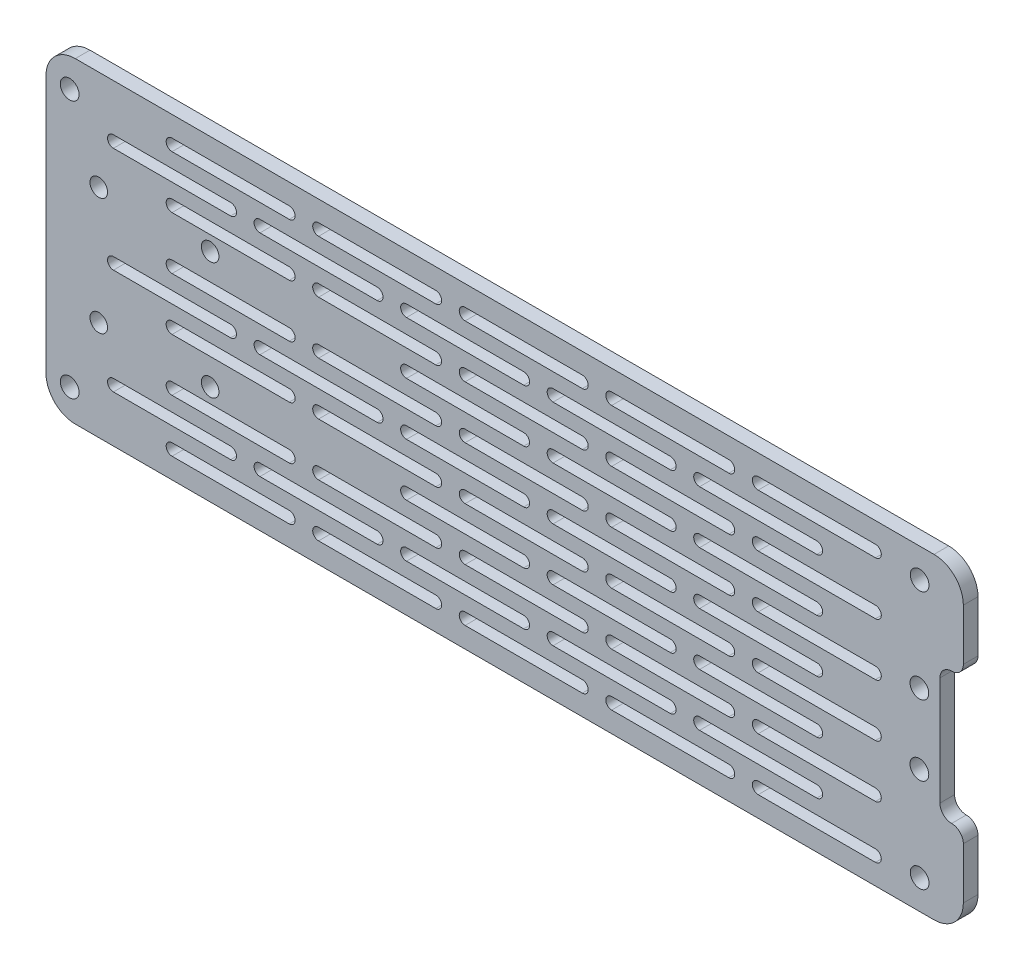
SolidWorks part; units mm, degrees
ref_plane "前视基准面" through (0, 0, 0) normal (0, 0, 1) x (1, 0, 0)
ref_plane "上视基准面" through (0, 0, 0) normal (0, 1, 0) x (1, 0, 0)
ref_plane "右视基准面" through (0, 0, 0) normal (1, 0, 0) x (0, 0, -1)
other "Configuration Table"
sketch "草图1" plane through (0, 0, 0) normal (0, 0, 1) x (1, 0, 0)
  line L1 (3.3, 37) -> (-153.2, 37)
  line L2 (3.3, 37) -> (3.3, -17)
  line L3 (3.3, -17) -> (-153.2, -17)
  line L4 (-153.2, 37) -> (-153.2, -17)
  dimension "D1" = 156.5
extrude "凸台-拉伸1" add sketch "草图1" along normal blind 2.5
fillet "圆角1" radius 5 4 edges at (-153.2, -17, 1.25) (-153.2, 37, 1.25) (3.3, 37, 1.25) (3.3, -17, 1.25)
sketch "草图2" plane through (0, 0, 2.5) normal (0, 0, 1) x (1, 0, 0)
  line L0 (-104.525, 10) -> (80.9664, 10) construction
  line L1 (-148.2, -17) -> (-1.7, -17) construction
  line L3 (-1.7, 37) -> (-148.2, 37) construction
  line L4 (3.3, -12) -> (3.3, 32) construction
  line L5 (3.3, -1.25) -> (-0.7, -1.25)
  line L6 (3.3, -1.25) -> (3.3, 21.25)
  line L7 (3.3, 21.25) -> (-0.7, 21.25)
  line L8 (-0.7, -1.25) -> (-0.7, 21.25)
  line L9 (-74.95, 71.5173) -> (-74.95, -58.776) construction
  line L10 (-153.2, 32) -> (-153.2, -12) construction
  line L11 (-45.375, 10) -> (-230.8664, 10) construction
  line L19 (-150.7, 27) -> (-142.7, 27) construction
  line L20 (-150.7, 27) -> (-150.7, 13.5) construction
  line L21 (-150.7, 13.5) -> (-118.7, 13.5) construction
  line L22 (-118.7, 27) -> (-118.7, 13.5) construction
  line L25 (-142.7, 27) -> (-142.7, 23.5) construction
  line L27 (-142.7, 23.5) -> (-126.7, 23.5) construction
  line L28 (-126.7, 23.5) -> (-126.7, 27) construction
  line L29 (-126.7, 27) -> (-118.7, 27) construction
  circle A0 centre (-4.2, 4) radius 1.6
  circle A1 centre (-4.2, 16) radius 1.6
  circle A11 centre (-125.2, 20) radius 1.5
  circle A12 centre (-144.2, 20) radius 1.5
  circle A13 centre (-125.2, 0) radius 1.5
  circle A14 centre (-144.2, 0) radius 1.5
  point P26 (-138.1207, 10)
  point P29 (-125.2, 18.5)
  point P30 (-123.7, 20)
  point P43 (-138.1207, 10)
  point P52 (-133.2793, 10)
  dimension "D4" = 3.2
  dimension "D8" = 5
  dimension "D11" = 19
  dimension "D12" = 2.5
  dimension "D13" = 13.5
  dimension "D16" = 10
  dimension "D9" = 3
  dimension "D10" = 3
  dimension "D1" = 4
  dimension "D2" = 7.5
  dimension "D3" = 12
  dimension "D5" = 22.5
  dimension "D6" = 32
  dimension "D7" = 5
  dimension "D15" = 8
  dimension "D14" = 16
  dimension "D17" = 3.5
  dimension "D18" = 19
extrude "切除-拉伸1" cut sketch "草图2" against normal up to next contours A1 | A0 | L6 L5 L8 L7 | A12 | A11 | A14 | A13
fillet "圆角5" radius 2 4 edges at (3.3, 21.25, 1.25) (-0.7, 21.25, 1.25) (-0.7, -1.25, 1.25) (3.3, -1.25, 1.25)
sketch "草图3" plane through (0, 0, 2.5) normal (0, 0, 1) x (1, 0, 0)
  line L1 (-156.66, 39.5) -> (-156.66, 114.5) construction
  line L2 (3.34, 37.5) -> (-156.66, 37.5) construction
  line L3 (-76.66, -135.6292) -> (-76.66, 162.1553) construction
  line L4 (-198.0876, 10) -> (29.1796, 10) construction
  line L5 (-156.66, -19.5) -> (-156.66, -100.5) construction
  line L6 (3.34, -19.5) -> (3.34, -100.5) construction
  line L7 (-148.2, -17) -> (-1.7, -17) construction
  line L8 (-1.7, 37) -> (-148.2, 37) construction
  line L9 (3.34, 114.5) -> (3.34, 39.5) construction
  line L10 (-156.66, 30.7638) -> (-156.66, 35.5) construction
  circle A0 centre (-149.16, 32) radius 1.6
  circle A1 centre (-149.16, -12) radius 1.6
  circle A2 centre (-4.16, 32) radius 1.6
  circle A3 centre (-4.16, -12) radius 1.6
  dimension "D1" = 3.2
  dimension "D2" = 7.5
  dimension "D3" = 5.5
  dimension "D4" = 45.6
extrude "切除-拉伸2" cut sketch "草图3" against normal up to next
sketch "草图4" plane through (0, 0, 2.5) normal (0, 0, 1) x (1, 0, 0)
  line L0 (-11.7, -12.5) -> (-31.7, -12.5) construction
  line L1 (-11.7, -13.5) -> (-31.7, -13.5)
  line L2 (-11.7, -11.5) -> (-31.7, -11.5)
  line L3 (3.3, -12) -> (3.3, -3.25) construction
  line L4 (-148.2, -17) -> (-1.7, -17) construction
  line L5 (-111.7, -12.5) -> (-131.7, -12.5) construction
  line L7 (-11.7, -2.5) -> (-31.7, -2.5)
  line L8 (-11.7, -4.5) -> (-31.7, -4.5)
  line L9 (-11.7, -3.5) -> (-31.7, -3.5) construction
  line L10 (-11.7, 6.5) -> (-31.7, 6.5)
  line L11 (-11.7, 4.5) -> (-31.7, 4.5)
  line L12 (-11.7, 5.5) -> (-31.7, 5.5) construction
  line L13 (-11.7, 15.5) -> (-31.7, 15.5)
  line L14 (-11.7, 13.5) -> (-31.7, 13.5)
  line L15 (-11.7, 14.5) -> (-31.7, 14.5) construction
  line L16 (-11.7, 24.5) -> (-31.7, 24.5)
  line L17 (-11.7, 22.5) -> (-31.7, 22.5)
  line L18 (-11.7, 23.5) -> (-31.7, 23.5) construction
  line L19 (-11.7, 33.5) -> (-31.7, 33.5)
  line L20 (-11.7, 31.5) -> (-31.7, 31.5)
  line L21 (-11.7, 32.5) -> (-31.7, 32.5) construction
  line L22 (-11.7, -11.5) -> (-11.7, -2.5) construction
  line L23 (-41.7, -8) -> (-21.7, -8) construction
  line L24 (-41.7, -7) -> (-21.7, -7)
  line L25 (-41.7, -9) -> (-21.7, -9)
  line L26 (-41.7, 0) -> (-21.7, 0)
  line L27 (-41.7, 2) -> (-21.7, 2)
  line L28 (-41.7, 1) -> (-21.7, 1) construction
  line L29 (-41.7, 9) -> (-21.7, 9)
  line L30 (-41.7, 11) -> (-21.7, 11)
  line L31 (-41.7, 10) -> (-21.7, 10) construction
  line L32 (-41.7, 18) -> (-21.7, 18)
  line L33 (-41.7, 20) -> (-21.7, 20)
  line L34 (-41.7, 19) -> (-21.7, 19) construction
  line L35 (-41.7, 27) -> (-21.7, 27)
  line L36 (-41.7, 29) -> (-21.7, 29)
  line L37 (-41.7, 28) -> (-21.7, 28) construction
  line L38 (-116.7, -8) -> (-96.7, -8) construction
  line L39 (-36.7, -11.5) -> (-36.7, -2.5) construction
  line L40 (-36.7, -12.5) -> (-56.7, -12.5) construction
  line L41 (-36.7, -13.5) -> (-56.7, -13.5)
  line L42 (-36.7, -11.5) -> (-56.7, -11.5)
  line L43 (-36.7, -3.5) -> (-56.7, -3.5) construction
  line L44 (-36.7, -4.5) -> (-56.7, -4.5)
  line L45 (-36.7, -2.5) -> (-56.7, -2.5)
  line L46 (-36.7, 5.5) -> (-56.7, 5.5) construction
  line L47 (-36.7, 4.5) -> (-56.7, 4.5)
  line L48 (-36.7, 6.5) -> (-56.7, 6.5)
  line L49 (-36.7, 14.5) -> (-56.7, 14.5) construction
  line L50 (-36.7, 13.5) -> (-56.7, 13.5)
  line L51 (-36.7, 15.5) -> (-56.7, 15.5)
  line L52 (-36.7, 23.5) -> (-56.7, 23.5) construction
  line L53 (-36.7, 22.5) -> (-56.7, 22.5)
  line L54 (-36.7, 24.5) -> (-56.7, 24.5)
  line L55 (-36.7, 32.5) -> (-56.7, 32.5) construction
  line L56 (-36.7, 31.5) -> (-56.7, 31.5)
  line L57 (-36.7, 33.5) -> (-56.7, 33.5)
  line L58 (-66.7, -8) -> (-46.7, -8) construction
  line L59 (-66.7, -7) -> (-46.7, -7)
  line L60 (-66.7, -9) -> (-46.7, -9)
  line L61 (-66.7, 1) -> (-46.7, 1) construction
  line L62 (-66.7, 2) -> (-46.7, 2)
  line L63 (-66.7, 0) -> (-46.7, 0)
  line L64 (-66.7, 10) -> (-46.7, 10) construction
  line L65 (-66.7, 11) -> (-46.7, 11)
  line L66 (-66.7, 9) -> (-46.7, 9)
  line L67 (-66.7, 19) -> (-46.7, 19) construction
  line L68 (-66.7, 20) -> (-46.7, 20)
  line L69 (-66.7, 18) -> (-46.7, 18)
  line L70 (-66.7, 28) -> (-46.7, 28) construction
  line L71 (-66.7, 29) -> (-46.7, 29)
  line L72 (-66.7, 27) -> (-46.7, 27)
  line L73 (-61.7, -11.5) -> (-61.7, -2.5) construction
  line L74 (-61.7, -12.5) -> (-81.7, -12.5) construction
  line L75 (-61.7, -13.5) -> (-81.7, -13.5)
  line L76 (-61.7, -11.5) -> (-81.7, -11.5)
  line L77 (-61.7, -3.5) -> (-81.7, -3.5) construction
  line L78 (-61.7, -4.5) -> (-81.7, -4.5)
  line L79 (-61.7, -2.5) -> (-81.7, -2.5)
  line L80 (-61.7, 5.5) -> (-81.7, 5.5) construction
  line L81 (-61.7, 4.5) -> (-81.7, 4.5)
  line L82 (-61.7, 6.5) -> (-81.7, 6.5)
  line L83 (-61.7, 14.5) -> (-81.7, 14.5) construction
  line L84 (-61.7, 13.5) -> (-81.7, 13.5)
  line L85 (-61.7, 15.5) -> (-81.7, 15.5)
  line L86 (-61.7, 23.5) -> (-81.7, 23.5) construction
  line L87 (-61.7, 22.5) -> (-81.7, 22.5)
  line L88 (-61.7, 24.5) -> (-81.7, 24.5)
  line L89 (-61.7, 32.5) -> (-81.7, 32.5) construction
  line L90 (-61.7, 31.5) -> (-81.7, 31.5)
  line L91 (-61.7, 33.5) -> (-81.7, 33.5)
  line L92 (-91.7, -8) -> (-71.7, -8) construction
  line L93 (-91.7, -7) -> (-71.7, -7)
  line L94 (-91.7, -9) -> (-71.7, -9)
  line L95 (-91.7, 1) -> (-71.7, 1) construction
  line L96 (-91.7, 2) -> (-71.7, 2)
  line L97 (-91.7, 0) -> (-71.7, 0)
  line L98 (-91.7, 10) -> (-71.7, 10) construction
  line L99 (-91.7, 11) -> (-71.7, 11)
  line L100 (-91.7, 9) -> (-71.7, 9)
  line L101 (-91.7, 19) -> (-71.7, 19) construction
  line L102 (-91.7, 20) -> (-71.7, 20)
  line L103 (-91.7, 18) -> (-71.7, 18)
  line L104 (-91.7, 28) -> (-71.7, 28) construction
  line L105 (-91.7, 29) -> (-71.7, 29)
  line L106 (-91.7, 27) -> (-71.7, 27)
  line L107 (-86.7, -11.5) -> (-86.7, -2.5) construction
  line L108 (-86.7, -12.5) -> (-106.7, -12.5) construction
  line L109 (-86.7, -13.5) -> (-106.7, -13.5)
  line L110 (-86.7, -11.5) -> (-106.7, -11.5)
  line L111 (-86.7, -3.5) -> (-106.7, -3.5) construction
  line L112 (-86.7, -4.5) -> (-106.7, -4.5)
  line L113 (-86.7, -2.5) -> (-106.7, -2.5)
  line L114 (-86.7, 5.5) -> (-106.7, 5.5) construction
  line L115 (-86.7, 4.5) -> (-106.7, 4.5)
  line L116 (-86.7, 6.5) -> (-106.7, 6.5)
  line L117 (-86.7, 14.5) -> (-106.7, 14.5) construction
  line L118 (-86.7, 13.5) -> (-106.7, 13.5)
  line L119 (-86.7, 15.5) -> (-106.7, 15.5)
  line L120 (-86.7, 23.5) -> (-106.7, 23.5) construction
  line L121 (-86.7, 22.5) -> (-106.7, 22.5)
  line L122 (-86.7, 24.5) -> (-106.7, 24.5)
  line L123 (-86.7, 32.5) -> (-106.7, 32.5) construction
  line L124 (-86.7, 31.5) -> (-106.7, 31.5)
  line L125 (-86.7, 33.5) -> (-106.7, 33.5)
  line L129 (-111.7, -13.5) -> (-131.7, -13.5)
  line L138 (-111.7, -11.5) -> (-131.7, -11.5)
  line L141 (-11.7, -11.5) -> (-36.7, -11.5) construction
  line L148 (-111.7, -3.5) -> (-131.7, -3.5) construction
  line L151 (-111.7, -4.5) -> (-131.7, -4.5)
  line L154 (-111.7, -2.5) -> (-131.7, -2.5)
  line L157 (-111.7, 5.5) -> (-131.7, 5.5) construction
  line L160 (-111.7, 4.5) -> (-131.7, 4.5)
  line L163 (-111.7, 6.5) -> (-131.7, 6.5)
  line L166 (-111.7, 14.5) -> (-131.7, 14.5) construction
  line L171 (-111.7, 13.5) -> (-131.7, 13.5)
  line L172 (-111.7, 15.5) -> (-131.7, 15.5)
  line L173 (-111.7, 23.5) -> (-131.7, 23.5) construction
  line L174 (-111.7, 22.5) -> (-131.7, 22.5)
  line L175 (-111.7, 24.5) -> (-131.7, 24.5)
  line L176 (-111.7, 32.5) -> (-131.7, 32.5) construction
  line L177 (-111.7, 31.5) -> (-131.7, 31.5)
  line L178 (-111.7, 33.5) -> (-131.7, 33.5)
  line L179 (-116.7, -7) -> (-96.7, -7)
  line L180 (-116.7, -9) -> (-96.7, -9)
  line L181 (-116.7, 10) -> (-96.7, 10) construction
  line L182 (-116.7, 11) -> (-96.7, 11)
  line L183 (-116.7, 9) -> (-96.7, 9)
  line L184 (-116.7, 28) -> (-96.7, 28) construction
  line L185 (-116.7, 29) -> (-96.7, 29)
  line L186 (-116.7, 27) -> (-96.7, 27)
  line L187 (-141.7, -8) -> (-121.7, -8) construction
  line L188 (-141.7, -7) -> (-121.7, -7)
  line L189 (-141.7, -9) -> (-121.7, -9)
  line L190 (-141.7, 10) -> (-121.7, 10) construction
  line L191 (-141.7, 11) -> (-121.7, 11)
  line L192 (-141.7, 9) -> (-121.7, 9)
  line L193 (-141.7, 28) -> (-121.7, 28) construction
  line L194 (-141.7, 29) -> (-121.7, 29)
  line L195 (-141.7, 27) -> (-121.7, 27)
  line L1242 (-116.7, -8) -> (-96.7, -8) construction
  line L1243 (-116.7, -7) -> (-96.7, -7) [skipped]
  line L1244 (-116.7, -9) -> (-96.7, -9) [skipped]
  line L1245 (-116.7, 1) -> (-96.7, 1) construction
  line L1246 (-116.7, 2) -> (-96.7, 2) [skipped]
  line L1247 (-116.7, 0) -> (-96.7, 0) [skipped]
  line L1248 (-116.7, 10) -> (-96.7, 10) construction
  line L1249 (-116.7, 11) -> (-96.7, 11) [skipped]
  line L1250 (-116.7, 9) -> (-96.7, 9) [skipped]
  line L1251 (-116.7, 19) -> (-96.7, 19) construction
  line L1252 (-116.7, 20) -> (-96.7, 20) [skipped]
  line L1253 (-116.7, 18) -> (-96.7, 18) [skipped]
  line L1254 (-116.7, 28) -> (-96.7, 28) construction
  line L1255 (-116.7, 29) -> (-96.7, 29) [skipped]
  line L1256 (-116.7, 27) -> (-96.7, 27) [skipped]
  line L1257 (-116.7, -8) -> (-96.7, -8) construction
  line L1258 (-116.7, -7) -> (-96.7, -7) [skipped]
  line L1259 (-116.7, -9) -> (-96.7, -9) [skipped]
  line L1260 (-116.7, 1) -> (-96.7, 1) construction
  line L1261 (-116.7, 2) -> (-96.7, 2) [skipped]
  line L1262 (-116.7, 0) -> (-96.7, 0) [skipped]
  line L1263 (-116.7, 10) -> (-96.7, 10) construction
  line L1264 (-116.7, 11) -> (-96.7, 11) [skipped]
  line L1265 (-116.7, 9) -> (-96.7, 9) [skipped]
  line L1266 (-116.7, 19) -> (-96.7, 19) construction
  line L1267 (-116.7, 20) -> (-96.7, 20) [skipped]
  line L1268 (-116.7, 18) -> (-96.7, 18) [skipped]
  line L1269 (-116.7, 28) -> (-96.7, 28) construction
  line L1270 (-116.7, 29) -> (-96.7, 29) [skipped]
  line L1271 (-116.7, 27) -> (-96.7, 27) [skipped]
  arc A0 (-11.7, -13.5) -> (-11.7, -11.5) centre (-11.7, -12.5) ccw
  arc A1 (-31.7, -11.5) -> (-31.7, -13.5) centre (-31.7, -12.5) ccw
  arc A2 (-11.7, -4.5) -> (-11.7, -2.5) centre (-11.7, -3.5) ccw
  arc A3 (-31.7, -2.5) -> (-31.7, -4.5) centre (-31.7, -3.5) ccw
  arc A4 (-11.7, 4.5) -> (-11.7, 6.5) centre (-11.7, 5.5) ccw
  arc A5 (-31.7, 6.5) -> (-31.7, 4.5) centre (-31.7, 5.5) ccw
  arc A6 (-11.7, 13.5) -> (-11.7, 15.5) centre (-11.7, 14.5) ccw
  arc A7 (-31.7, 15.5) -> (-31.7, 13.5) centre (-31.7, 14.5) ccw
  arc A8 (-11.7, 22.5) -> (-11.7, 24.5) centre (-11.7, 23.5) ccw
  arc A9 (-31.7, 24.5) -> (-31.7, 22.5) centre (-31.7, 23.5) ccw
  arc A10 (-11.7, 31.5) -> (-11.7, 33.5) centre (-11.7, 32.5) ccw
  arc A11 (-31.7, 33.5) -> (-31.7, 31.5) centre (-31.7, 32.5) ccw
  arc A12 (-41.7, -7) -> (-41.7, -9) centre (-41.7, -8) ccw
  arc A13 (-21.7, -9) -> (-21.7, -7) centre (-21.7, -8) ccw
  arc A14 (-41.7, 2) -> (-41.7, 0) centre (-41.7, 1) ccw
  arc A15 (-21.7, 0) -> (-21.7, 2) centre (-21.7, 1) ccw
  arc A16 (-41.7, 11) -> (-41.7, 9) centre (-41.7, 10) ccw
  arc A17 (-21.7, 9) -> (-21.7, 11) centre (-21.7, 10) ccw
  arc A18 (-41.7, 20) -> (-41.7, 18) centre (-41.7, 19) ccw
  arc A19 (-21.7, 18) -> (-21.7, 20) centre (-21.7, 19) ccw
  arc A20 (-41.7, 29) -> (-41.7, 27) centre (-41.7, 28) ccw
  arc A21 (-21.7, 27) -> (-21.7, 29) centre (-21.7, 28) ccw
  arc A22 (-36.7, -13.5) -> (-36.7, -11.5) centre (-36.7, -12.5) ccw
  arc A23 (-56.7, -11.5) -> (-56.7, -13.5) centre (-56.7, -12.5) ccw
  arc A24 (-36.7, -4.5) -> (-36.7, -2.5) centre (-36.7, -3.5) ccw
  arc A25 (-56.7, -2.5) -> (-56.7, -4.5) centre (-56.7, -3.5) ccw
  arc A26 (-36.7, 4.5) -> (-36.7, 6.5) centre (-36.7, 5.5) ccw
  arc A27 (-56.7, 6.5) -> (-56.7, 4.5) centre (-56.7, 5.5) ccw
  arc A28 (-36.7, 13.5) -> (-36.7, 15.5) centre (-36.7, 14.5) ccw
  arc A29 (-56.7, 15.5) -> (-56.7, 13.5) centre (-56.7, 14.5) ccw
  arc A30 (-36.7, 22.5) -> (-36.7, 24.5) centre (-36.7, 23.5) ccw
  arc A31 (-56.7, 24.5) -> (-56.7, 22.5) centre (-56.7, 23.5) ccw
  arc A32 (-36.7, 31.5) -> (-36.7, 33.5) centre (-36.7, 32.5) ccw
  arc A33 (-56.7, 33.5) -> (-56.7, 31.5) centre (-56.7, 32.5) ccw
  arc A34 (-66.7, -7) -> (-66.7, -9) centre (-66.7, -8) ccw
  arc A35 (-46.7, -9) -> (-46.7, -7) centre (-46.7, -8) ccw
  arc A36 (-66.7, 2) -> (-66.7, 0) centre (-66.7, 1) ccw
  arc A37 (-46.7, 0) -> (-46.7, 2) centre (-46.7, 1) ccw
  arc A38 (-66.7, 11) -> (-66.7, 9) centre (-66.7, 10) ccw
  arc A39 (-46.7, 9) -> (-46.7, 11) centre (-46.7, 10) ccw
  arc A40 (-66.7, 20) -> (-66.7, 18) centre (-66.7, 19) ccw
  arc A41 (-46.7, 18) -> (-46.7, 20) centre (-46.7, 19) ccw
  arc A42 (-66.7, 29) -> (-66.7, 27) centre (-66.7, 28) ccw
  arc A43 (-46.7, 27) -> (-46.7, 29) centre (-46.7, 28) ccw
  arc A44 (-61.7, -13.5) -> (-61.7, -11.5) centre (-61.7, -12.5) ccw
  arc A45 (-81.7, -11.5) -> (-81.7, -13.5) centre (-81.7, -12.5) ccw
  arc A46 (-61.7, -4.5) -> (-61.7, -2.5) centre (-61.7, -3.5) ccw
  arc A47 (-81.7, -2.5) -> (-81.7, -4.5) centre (-81.7, -3.5) ccw
  arc A48 (-61.7, 4.5) -> (-61.7, 6.5) centre (-61.7, 5.5) ccw
  arc A49 (-81.7, 6.5) -> (-81.7, 4.5) centre (-81.7, 5.5) ccw
  arc A50 (-61.7, 13.5) -> (-61.7, 15.5) centre (-61.7, 14.5) ccw
  arc A51 (-81.7, 15.5) -> (-81.7, 13.5) centre (-81.7, 14.5) ccw
  arc A52 (-61.7, 22.5) -> (-61.7, 24.5) centre (-61.7, 23.5) ccw
  arc A53 (-81.7, 24.5) -> (-81.7, 22.5) centre (-81.7, 23.5) ccw
  arc A54 (-61.7, 31.5) -> (-61.7, 33.5) centre (-61.7, 32.5) ccw
  arc A55 (-81.7, 33.5) -> (-81.7, 31.5) centre (-81.7, 32.5) ccw
  arc A56 (-91.7, -7) -> (-91.7, -9) centre (-91.7, -8) ccw
  arc A57 (-71.7, -9) -> (-71.7, -7) centre (-71.7, -8) ccw
  arc A58 (-91.7, 2) -> (-91.7, 0) centre (-91.7, 1) ccw
  arc A59 (-71.7, 0) -> (-71.7, 2) centre (-71.7, 1) ccw
  arc A60 (-91.7, 11) -> (-91.7, 9) centre (-91.7, 10) ccw
  arc A61 (-71.7, 9) -> (-71.7, 11) centre (-71.7, 10) ccw
  arc A62 (-91.7, 20) -> (-91.7, 18) centre (-91.7, 19) ccw
  arc A63 (-71.7, 18) -> (-71.7, 20) centre (-71.7, 19) ccw
  arc A64 (-91.7, 29) -> (-91.7, 27) centre (-91.7, 28) ccw
  arc A65 (-71.7, 27) -> (-71.7, 29) centre (-71.7, 28) ccw
  arc A66 (-86.7, -13.5) -> (-86.7, -11.5) centre (-86.7, -12.5) ccw
  arc A67 (-106.7, -11.5) -> (-106.7, -13.5) centre (-106.7, -12.5) ccw
  arc A68 (-86.7, -4.5) -> (-86.7, -2.5) centre (-86.7, -3.5) ccw
  arc A69 (-106.7, -2.5) -> (-106.7, -4.5) centre (-106.7, -3.5) ccw
  arc A70 (-86.7, 4.5) -> (-86.7, 6.5) centre (-86.7, 5.5) ccw
  arc A71 (-106.7, 6.5) -> (-106.7, 4.5) centre (-106.7, 5.5) ccw
  arc A72 (-86.7, 13.5) -> (-86.7, 15.5) centre (-86.7, 14.5) ccw
  arc A73 (-106.7, 15.5) -> (-106.7, 13.5) centre (-106.7, 14.5) ccw
  arc A74 (-86.7, 22.5) -> (-86.7, 24.5) centre (-86.7, 23.5) ccw
  arc A75 (-106.7, 24.5) -> (-106.7, 22.5) centre (-106.7, 23.5) ccw
  arc A76 (-86.7, 31.5) -> (-86.7, 33.5) centre (-86.7, 32.5) ccw
  arc A77 (-106.7, 33.5) -> (-106.7, 31.5) centre (-106.7, 32.5) ccw
  arc A114 (-111.7, -13.5) -> (-111.7, -11.5) centre (-111.7, -12.5) ccw
  arc A115 (-131.7, -11.5) -> (-131.7, -13.5) centre (-131.7, -12.5) ccw
  arc A116 (-111.7, -4.5) -> (-111.7, -2.5) centre (-111.7, -3.5) ccw
  arc A117 (-131.7, -2.5) -> (-131.7, -4.5) centre (-131.7, -3.5) ccw
  arc A118 (-111.7, 4.5) -> (-111.7, 6.5) centre (-111.7, 5.5) ccw
  arc A119 (-131.7, 6.5) -> (-131.7, 4.5) centre (-131.7, 5.5) ccw
  arc A120 (-111.7, 13.5) -> (-111.7, 15.5) centre (-111.7, 14.5) ccw
  arc A121 (-131.7, 15.5) -> (-131.7, 13.5) centre (-131.7, 14.5) ccw
  arc A122 (-111.7, 22.5) -> (-111.7, 24.5) centre (-111.7, 23.5) ccw
  arc A123 (-131.7, 24.5) -> (-131.7, 22.5) centre (-131.7, 23.5) ccw
  arc A124 (-111.7, 31.5) -> (-111.7, 33.5) centre (-111.7, 32.5) ccw
  arc A125 (-131.7, 33.5) -> (-131.7, 31.5) centre (-131.7, 32.5) ccw
  arc A126 (-116.7, -7) -> (-116.7, -9) centre (-116.7, -8) ccw
  arc A127 (-96.7, -9) -> (-96.7, -7) centre (-96.7, -8) ccw
  arc A128 (-116.7, 11) -> (-116.7, 9) centre (-116.7, 10) ccw
  arc A129 (-96.7, 9) -> (-96.7, 11) centre (-96.7, 10) ccw
  arc A130 (-116.7, 29) -> (-116.7, 27) centre (-116.7, 28) ccw
  arc A131 (-96.7, 27) -> (-96.7, 29) centre (-96.7, 28) ccw
  arc A132 (-141.7, -7) -> (-141.7, -9) centre (-141.7, -8) ccw
  arc A133 (-121.7, -9) -> (-121.7, -7) centre (-121.7, -8) ccw
  arc A134 (-141.7, 11) -> (-141.7, 9) centre (-141.7, 10) ccw
  arc A135 (-121.7, 9) -> (-121.7, 11) centre (-121.7, 10) ccw
  arc A136 (-141.7, 29) -> (-141.7, 27) centre (-141.7, 28) ccw
  arc A137 (-121.7, 27) -> (-121.7, 29) centre (-121.7, 28) ccw
  arc A836 (-116.7, -7) -> (-116.7, -9) centre (-116.7, -8) ccw [skipped]
  arc A837 (-96.7, -9) -> (-96.7, -7) centre (-96.7, -8) ccw [skipped]
  arc A838 (-116.7, 2) -> (-116.7, 0) centre (-116.7, 1) ccw [skipped]
  arc A839 (-96.7, 0) -> (-96.7, 2) centre (-96.7, 1) ccw [skipped]
  arc A840 (-116.7, 11) -> (-116.7, 9) centre (-116.7, 10) ccw [skipped]
  arc A841 (-96.7, 9) -> (-96.7, 11) centre (-96.7, 10) ccw [skipped]
  arc A842 (-116.7, 20) -> (-116.7, 18) centre (-116.7, 19) ccw [skipped]
  arc A843 (-96.7, 18) -> (-96.7, 20) centre (-96.7, 19) ccw [skipped]
  arc A844 (-116.7, 29) -> (-116.7, 27) centre (-116.7, 28) ccw [skipped]
  arc A845 (-96.7, 27) -> (-96.7, 29) centre (-96.7, 28) ccw [skipped]
  point P2 (-21.7, -12.5)
  point P9 (-31.7, -8)
  point P15 (-21.7, -3.5)
  point P22 (-21.7, 5.5)
  point P29 (-21.7, 14.5)
  point P36 (-21.7, 23.5)
  point P43 (-21.7, 32.5)
  point P55 (-31.7, 1)
  point P63 (-31.7, 10)
  point P70 (-31.7, 19)
  point P77 (-31.7, 28)
  point P85 (-106.7, -8)
  point P89 (-46.7, -12.5)
  point P94 (-56.7, -8)
  point P98 (-46.7, -3.5)
  point P105 (-46.7, 5.5)
  point P112 (-46.7, 14.5)
  point P119 (-46.7, 23.5)
  point P126 (-46.7, 32.5)
  point P138 (-56.7, 1)
  point P145 (-56.7, 10)
  point P152 (-56.7, 19)
  point P159 (-56.7, 28)
  point P168 (-71.7, -12.5)
  point P173 (-81.7, -8)
  point P177 (-71.7, -3.5)
  point P184 (-71.7, 5.5)
  point P191 (-71.7, 14.5)
  point P198 (-71.7, 23.5)
  point P205 (-71.7, 32.5)
  point P217 (-81.7, 1)
  point P224 (-81.7, 10)
  point P231 (-81.7, 19)
  point P238 (-81.7, 28)
  point P247 (-96.7, -12.5)
  point P254 (-121.7, -12.5)
  point P256 (-96.7, -3.5)
  point P263 (-96.7, 5.5)
  point P270 (-96.7, 14.5)
  point P277 (-96.7, 23.5)
  point P284 (-96.7, 32.5)
  point P291 (-102.2793, 1)
  point P298 (-102.2793, 10)
  point P299 (-121.7, -3.5)
  point P305 (-102.2793, 19)
  point P307 (-121.7, 5.5)
  point P312 (-102.2793, 28)
  point P315 (-121.7, 14.5)
  point P322 (-121.7, 23.5)
  point P331 (-121.7, 32.5)
  point P342 (-102.2793, -8)
  point P343 (-106.7, 10)
  point P349 (-102.2793, -8)
  point P351 (-106.7, 28)
  point P356 (-102.2793, 1)
  point P359 (-131.7, -8)
  point P363 (-102.2793, 10)
  point P367 (-131.7, 10)
  point P370 (-102.2793, 19)
  point P375 (-131.7, 28)
  point P377 (-102.2793, 28)
  point P384 (-102.2793, -8)
  point P391 (-102.2793, 1)
  point P398 (-102.2793, 10)
  point P405 (-102.2793, 19)
  point P412 (-102.2793, 28)
  point P419 (-102.2793, -8)
  point P426 (-102.2793, 1)
  point P433 (-102.2793, 10)
  point P440 (-102.2793, 19)
  point P447 (-102.2793, 28)
  point P454 (-102.2793, -8)
  point P461 (-102.2793, 1)
  point P468 (-102.2793, 10)
  point P475 (-102.2793, 19)
  point P482 (-102.2793, 28)
  point P489 (-102.2793, -8)
  point P496 (-102.2793, 1)
  point P503 (-102.2793, 10)
  point P510 (-102.2793, 19)
  point P517 (-102.2793, 28)
  point P524 (-102.2793, -8)
  point P531 (-102.2793, 1)
  point P538 (-102.2793, 10)
  point P545 (-102.2793, 19)
  point P552 (-102.2793, 28)
  point P559 (-102.2793, -8)
  point P566 (-102.2793, 1)
  point P573 (-102.2793, 10)
  point P580 (-102.2793, 19)
  point P587 (-102.2793, 28)
  point P594 (-102.2, -8)
  point P601 (-102.2, 1)
  point P608 (-102.2, 10)
  point P615 (-102.2, 19)
  point P622 (-102.2, 28)
  point P629 (-102.2, -8)
  point P636 (-102.2, 1)
  point P643 (-102.2, 10)
  point P650 (-102.2, 19)
  point P657 (-102.2, 28)
  point P664 (-102.2, -8)
  point P671 (-102.2, 1)
  point P678 (-102.2, 10)
  point P685 (-102.2, 19)
  point P692 (-102.2, 28)
  point P699 (-102.2, -8)
  point P706 (-102.2, 1)
  point P713 (-102.2, 10)
  point P720 (-102.2, 19)
  point P727 (-102.2, 28)
  point P734 (-102.2, -8)
  point P741 (-102.2, 1)
  point P748 (-102.2, 10)
  point P755 (-102.2, 19)
  point P762 (-102.2, 28)
  point P769 (-102.2, -8)
  point P776 (-102.2, 1)
  point P783 (-102.2, 10)
  point P790 (-102.2, 19)
  point P797 (-102.2, 28)
  point P804 (-102.2, -8)
  point P811 (-102.2, 1)
  point P818 (-102.2, 10)
  point P825 (-102.2, 19)
  point P832 (-102.2, 28)
  point P839 (-102.2, -8)
  point P846 (-102.2, 1)
  point P853 (-102.2, 10)
  point P860 (-102.2, 19)
  point P867 (-102.2, 28)
  point P874 (-107.26, -8)
  point P881 (-107.26, 1)
  point P888 (-107.26, 10)
  point P895 (-107.26, 19)
  point P902 (-107.26, 28)
  point P909 (-107.26, -8)
  point P916 (-107.26, 1)
  point P923 (-107.26, 10)
  point P930 (-107.26, 19)
  point P937 (-107.26, 28)
  point P944 (-106.2, -8)
  point P951 (-106.2, 1)
  point P958 (-106.2, 10)
  point P965 (-106.2, 19)
  point P972 (-106.2, 28)
  point P979 (-106.2, -8)
  point P986 (-106.2, 1)
  point P993 (-106.2, 10)
  point P1000 (-106.2, 19)
  point P1007 (-106.2, 28)
  point P1014 (-106.2, -8)
  point P1021 (-106.2, 1)
  point P1028 (-106.2, 10)
  point P1035 (-106.2, 19)
  point P1042 (-106.2, 28)
  point P1049 (-106.2, -8)
  point P1056 (-106.2, 1)
  point P1063 (-106.2, 10)
  point P1070 (-106.2, 19)
  point P1077 (-106.2, 28)
  point P1084 (-106.2, -8)
  point P1091 (-106.2, 1)
  point P1098 (-106.2, 10)
  point P1105 (-106.2, 19)
  point P1112 (-106.2, 28)
  point P1119 (-106.2, -8)
  point P1126 (-106.2, 1)
  point P1133 (-106.2, 10)
  point P1140 (-106.2, 19)
  point P1147 (-106.2, 28)
  point P1154 (-106.2, -8)
  point P1161 (-106.2, 1)
  point P1168 (-106.2, 10)
  point P1175 (-106.2, 19)
  point P1182 (-106.2, 28)
  point P1189 (-106.2, -8)
  point P1196 (-106.2, 1)
  point P1203 (-106.2, 10)
  point P1210 (-106.2, 19)
  point P1217 (-106.2, 28)
  point P1224 (-106.2, -8)
  point P1231 (-106.2, 1)
  point P1238 (-106.2, 10)
  point P1245 (-106.2, 19)
  point P1252 (-106.2, 28)
  point P1259 (-106.2, -8)
  point P1266 (-106.2, 1)
  point P1273 (-106.2, 10)
  point P1280 (-106.2, 19)
  point P1287 (-106.2, 28)
  point P1294 (-106.2, -8)
  point P1301 (-106.2, 1)
  point P1308 (-106.2, 10)
  point P1315 (-106.2, 19)
  point P1322 (-106.2, 28)
  point P1329 (-106.2, -8)
  point P1336 (-106.2, 1)
  point P1343 (-106.2, 10)
  point P1350 (-106.2, 19)
  point P1357 (-106.2, 28)
  point P1364 (-106.2, -8)
  point P1371 (-106.2, 1)
  point P1378 (-106.2, 10)
  point P1385 (-106.2, 19)
  point P1392 (-106.2, 28)
  point P1399 (-106.2, -8)
  point P1406 (-106.2, 1)
  point P1413 (-106.2, 10)
  point P1420 (-106.2, 19)
  point P1427 (-106.2, 28)
  point P1434 (-106.2, -8)
  point P1441 (-106.2, 1)
  point P1448 (-106.2, 10)
  point P1455 (-106.2, 19)
  point P1462 (-106.2, 28)
  point P1469 (-106.2, -8)
  point P1476 (-106.2, 1)
  point P1483 (-106.2, 10)
  point P1490 (-106.2, 19)
  point P1497 (-106.2, 28)
  point P1504 (-106.7, -8)
  point P1511 (-106.7, 1)
  point P1518 (-106.7, 10)
  point P1525 (-106.7, 19)
  point P1532 (-106.7, 28)
  point P1539 (-106.7, -8)
  point P1546 (-106.7, 1)
  point P1553 (-106.7, 10)
  point P1560 (-106.7, 19)
  point P1567 (-106.7, 28)
  point P1574 (-106.7, -8)
  point P1581 (-106.7, 1)
  point P1588 (-106.7, 10)
  point P1595 (-106.7, 19)
  point P1602 (-106.7, 28)
  point P1609 (-106.7, -8)
  point P1616 (-106.7, 1)
  point P1623 (-106.7, 10)
  point P1630 (-106.7, 19)
  point P1637 (-106.7, 28)
  point P1644 (-106.7, -8)
  point P1651 (-106.7, 1)
  point P1658 (-106.7, 10)
  point P1665 (-106.7, 19)
  point P1672 (-106.7, 28)
  point P1679 (-106.7, -8)
  point P1686 (-106.7, 1)
  point P1693 (-106.7, 10)
  point P1700 (-106.7, 19)
  point P1707 (-106.7, 28)
  point P1714 (-106.7, -8)
  point P1721 (-106.7, 1)
  point P1728 (-106.7, 10)
  point P1735 (-106.7, 19)
  point P1742 (-106.7, 28)
  point P1749 (-106.7, -8)
  point P1756 (-106.7, 1)
  point P1763 (-106.7, 10)
  point P1770 (-106.7, 19)
  point P1777 (-106.7, 28)
  point P1784 (-106.7, -8)
  point P1791 (-106.7, 1)
  point P1798 (-106.7, 10)
  point P1805 (-106.7, 19)
  point P1812 (-106.7, 28)
  point P1819 (-106.7, -8)
  point P1826 (-106.7, 1)
  point P1833 (-106.7, 10)
  point P1840 (-106.7, 19)
  point P1847 (-106.7, 28)
  point P1854 (-106.7, -8)
  point P1861 (-106.7, 1)
  point P1868 (-106.7, 10)
  point P1875 (-106.7, 19)
  point P1882 (-106.7, 28)
  point P1889 (-106.7, -8)
  point P1896 (-106.7, 1)
  point P1903 (-106.7, 10)
  point P1910 (-106.7, 19)
  point P1917 (-106.7, 28)
  point P1924 (-106.7, -8)
  point P1931 (-106.7, 1)
  point P1938 (-106.7, 10)
  point P1945 (-106.7, 19)
  point P1952 (-106.7, 28)
  point P1959 (-106.7, -8)
  point P1966 (-106.7, 1)
  point P1973 (-106.7, 10)
  point P1980 (-106.7, 19)
  point P1987 (-106.7, 28)
  point P1994 (-106.7, -8)
  point P2001 (-106.7, 1)
  point P2008 (-106.7, 10)
  point P2015 (-106.7, 19)
  point P2022 (-106.7, 28)
  point P2029 (-106.7, -8)
  point P2036 (-106.7, 1)
  point P2043 (-106.7, 10)
  point P2050 (-106.7, 19)
  point P2057 (-106.7, 28)
  point P2064 (-106.7, -8)
  point P2071 (-106.7, 1)
  point P2078 (-106.7, 10)
  point P2085 (-106.7, 19)
  point P2092 (-106.7, 28)
  point P2099 (-106.7, -8)
  point P2106 (-106.7, 1)
  point P2113 (-106.7, 10)
  point P2120 (-106.7, 19)
  point P2127 (-106.7, 28)
  point P2134 (-106.7, -8)
  point P2141 (-106.7, 1)
  point P2148 (-106.7, 10)
  point P2155 (-106.7, 19)
  point P2162 (-106.7, 28)
  point P2169 (-106.7, -8)
  point P2176 (-106.7, 1)
  point P2183 (-106.7, 10)
  point P2190 (-106.7, 19)
  point P2197 (-106.7, 28)
  point P2204 (-106.7, -8)
  point P2211 (-106.7, 1)
  point P2218 (-106.7, 10)
  point P2225 (-106.7, 19)
  point P2232 (-106.7, 28)
  point P2239 (-106.7, -8)
  point P2246 (-106.7, 1)
  point P2253 (-106.7, 10)
  point P2260 (-106.7, 19)
  point P2267 (-106.7, 28)
  point P2274 (-106.7, -8)
  point P2281 (-106.7, 1)
  point P2288 (-106.7, 10)
  point P2295 (-106.7, 19)
  point P2302 (-106.7, 28)
  point P2309 (-106.7, -8)
  point P2316 (-106.7, 1)
  point P2323 (-106.7, 10)
  point P2330 (-106.7, 19)
  point P2337 (-106.7, 28)
  point P2344 (-106.7, -8)
  point P2351 (-106.7, 1)
  point P2358 (-106.7, 10)
  point P2365 (-106.7, 19)
  point P2372 (-106.7, 28)
  point P2379 (-106.7, -8)
  point P2386 (-106.7, 1)
  point P2393 (-106.7, 10)
  point P2400 (-106.7, 19)
  point P2407 (-106.7, 28)
  point P2414 (-106.7, -8)
  point P2421 (-106.7, 1)
  point P2428 (-106.7, 10)
  point P2435 (-106.7, 19)
  point P2442 (-106.7, 28)
  point P2449 (-106.7, -8)
  point P2456 (-106.7, 1)
  point P2463 (-106.7, 10)
  point P2470 (-106.7, 19)
  point P2477 (-106.7, 28)
  point P2484 (-106.7, -8)
  point P2491 (-106.7, 1)
  point P2498 (-106.7, 10)
  point P2505 (-106.7, 19)
  point P2512 (-106.7, 28)
  point P2519 (-106.7, -8)
  point P2526 (-106.7, 1)
  point P2533 (-106.7, 10)
  point P2540 (-106.7, 19)
  point P2547 (-106.7, 28)
  point P2554 (-106.7, -8)
  point P2561 (-106.7, 1)
  point P2568 (-106.7, 10)
  point P2575 (-106.7, 19)
  point P2582 (-106.7, 28)
  point P2589 (-106.7, -8)
  point P2596 (-106.7, 1)
  point P2603 (-106.7, 10)
  point P2610 (-106.7, 19)
  point P2617 (-106.7, 28)
  point P2624 (-106.7, -8)
  point P2631 (-106.7, 1)
  point P2638 (-106.7, 10)
  point P2645 (-106.7, 19)
  point P2652 (-106.7, 28)
  point P2659 (-106.7, -8)
  point P2666 (-106.7, 1)
  point P2673 (-106.7, 10)
  point P2680 (-106.7, 19)
  point P2687 (-106.7, 28)
  point P2694 (-106.7, -8)
  point P2701 (-106.7, 1)
  point P2708 (-106.7, 10)
  point P2715 (-106.7, 19)
  point P2722 (-106.7, 28)
  point P2729 (-106.7, -8)
  point P2736 (-106.7, 1)
  point P2743 (-106.7, 10)
  point P2750 (-106.7, 19)
  point P2757 (-106.7, 28)
  point P2764 (-106.7, -8)
  point P2771 (-106.7, 1)
  point P2778 (-106.7, 10)
  point P2785 (-106.7, 19)
  point P2792 (-106.7, 28)
  point P2799 (-106.7, -8)
  point P2806 (-106.7, 1)
  point P2813 (-106.7, 10)
  point P2820 (-106.7, 19)
  point P2827 (-106.7, 28)
  point P2834 (-106.7, -8)
  point P2841 (-106.7, 1)
  point P2848 (-106.7, 10)
  point P2855 (-106.7, 19)
  point P2862 (-106.7, 28)
  point P2869 (-106.7, -8)
  point P2876 (-106.7, 1)
  point P2883 (-106.7, 10)
  point P2890 (-106.7, 19)
  point P2897 (-106.7, 28)
  point P2904 (-106.7, -8)
  point P2911 (-106.7, 1)
  point P2918 (-106.7, 10)
  point P2925 (-106.7, 19)
  point P2932 (-106.7, 28)
  dimension "D1" = 1
  dimension "D7" = 1
  dimension "D2" = 20
  dimension "D3" = 15
  dimension "D4" = 4.5
  dimension "D5" = 6
  dimension "D6" = 9
  dimension "D8" = 20
  dimension "D9" = 25
  dimension "D10" = 9
  dimension "D14" = 25
  dimension "D17" = 36
  dimension "D13" = 4
extrude "切除-拉伸3" cut sketch "草图4" against normal up to next (2.5 mm away)
